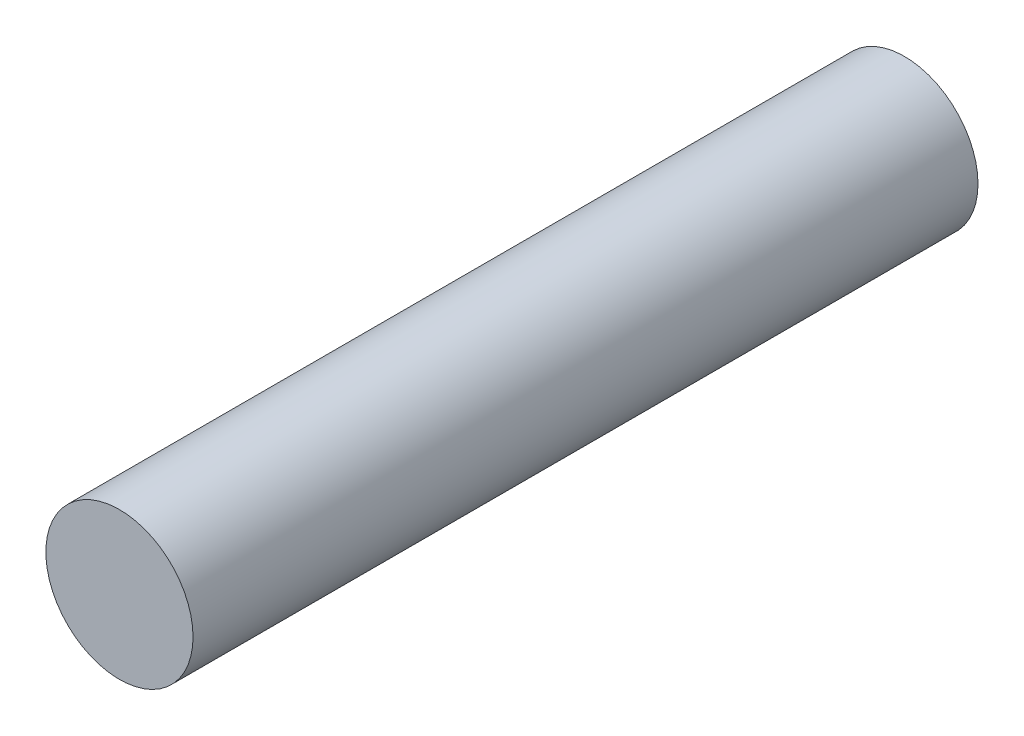
SolidWorks part; units mm, degrees
ref_plane "Front Plane" through (0, 0, 0) normal (0, 0, 1) x (1, 0, 0)
ref_plane "Top Plane" through (0, 0, 0) normal (0, 1, 0) x (1, 0, 0)
ref_plane "Right Plane" through (0, 0, 0) normal (1, 0, 0) x (0, 0, -1)
sketch "Sketch1" plane through (0, 0, 0) normal (0, 0, 1) x (1, 0, 0)
  circle A0 centre (0, 0) radius 7.5
extrude "Boss-Extrude1" add sketch "Sketch1" along normal blind 40 and the other way blind 40 contours A0
